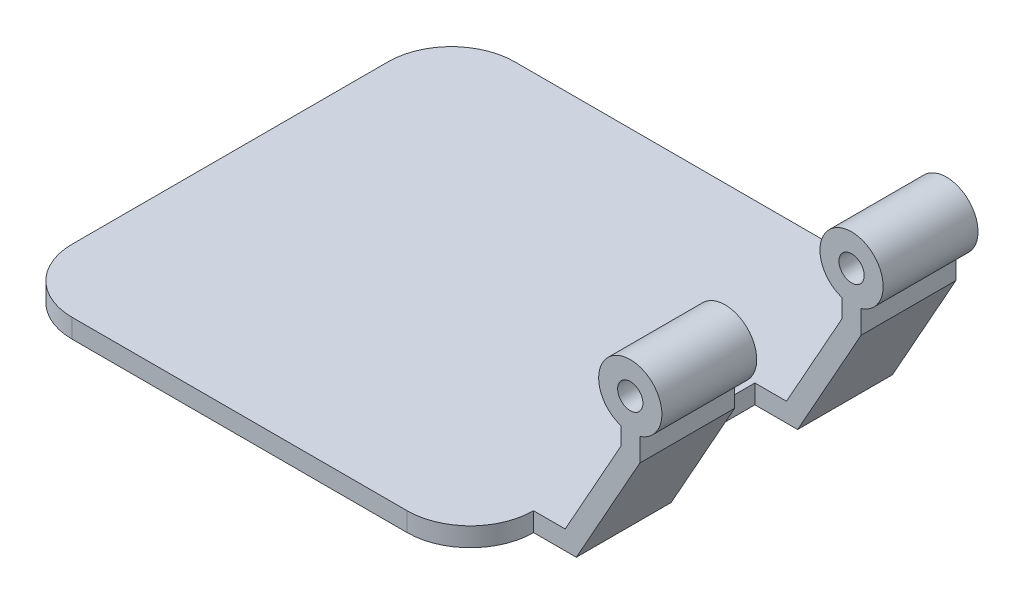
SolidWorks part; units mm, degrees
ref_plane "Front Plane" through (0, 0, 0) normal (0, 0, 1) x (1, 0, 0)
ref_plane "Top Plane" through (0, 0, 0) normal (0, 1, 0) x (1, 0, 0)
ref_plane "Right Plane" through (0, 0, 0) normal (1, 0, 0) x (0, 0, -1)
sketch "Sketch1" plane through (0, 0, 0) normal (0, 0, 1) x (1, 0, 0)
  line L0 (0, 3) -> (0, 0)
  line L1 (0, 0) -> (81.7588, 0)
  line L4 (88.7917, 18.7069) -> (80, 3)
  line L5 (80, 3) -> (0, 3)
  line L9 (81.7588, 0) -> (91.7917, 17.9244)
  line L11 (88.7917, 18.7069) -> (88.7917, 23.7069)
  line L12 (91.7917, 17.9244) -> (91.7917, 23.7069)
  line L13 (90.2917, 32.6026) -> (90.2917, 7.0815) construction
  line L14 (88.7917, 23.7069) -> (91.7917, 23.7069)
  circle A0 centre (90.2917, 26.3526) radius 5
  dimension "D9" = 10
  dimension "D1" = 80
  dimension "D2" = 3
  dimension "D3" = 18
  dimension "D4" = 3
  dimension "D5" = 119.237
  dimension "D6" = 5
  dimension "D7" = 3
  dimension "D8" = 1.5
extrude "Boss-Extrude1" add sketch "Sketch1" along normal blind 50 contours L9 L12 L14 L11 L4 L5 L0 L1 | A0
sketch "Sketch2" plane through (0, 0, 0) normal (0, 0, 1) x (1, 0, 0)
  circle A1 centre (90.2917, 26.3526) radius 2
  arc A2 (91.7917, 21.5829) -> (88.7917, 21.5829) centre (90.2917, 26.3526) ccw construction
  point P2 (88.697, 32.4609)
  point P11 (98.7108, 32.4609)
  point P12 (89.1184, 32.4609)
  point P13 (0, 0)
  point P14 (88.697, 32.4609)
  point P15 (88.697, 32.4609)
  dimension "D3" = 4
extrude "Cut-Extrude1" cut sketch "Sketch2" along normal through all
sketch "Sketch7" plane through (62.2541, -34.846, 0) normal (0.8726, -0.4884, 0) x (0, 0, -1)
  line L0 (-35, 89.9022) -> (-35, 28.0637) construction
  line L1 (-15, 89.9022) -> (-15, 25.2431) construction
  line L2 (-50, 39.9334) -> (-50, 60.4747) construction
  line L3 (0, 39.9334) -> (0, 60.4747) construction
  line L4 (-50, 39.9334) -> (0, 39.9334) construction
  line L5 (-35, 79.9206) -> (-15, 79.9206)
  line L6 (-35, 79.9206) -> (-35, 39.9334)
  line L7 (-35, 39.9334) -> (-15, 39.9334)
  line L8 (-15, 79.9206) -> (-15, 39.9334)
  point P6 (-35, 58.9829)
  dimension "D1" = 15
  dimension "D2" = 15
extrude "Cut-Extrude3" cut sketch "Sketch7" against normal blind 10 and the other way blind 10
sketch "Sketch8" plane through (0, 0, 0) normal (0, 0, 1) x (1, 0, 0)
  line L0 (66.951, 3) -> (66.951, 0)
  line L1 (80, 3) -> (0, 3) construction
  line L2 (0, 0) -> (81.7588, 0) construction
  line L3 (66.951, 0) -> (81.7588, 0)
  line L4 (81.7588, 0) -> (79.254, 1.6672)
  line L5 (88.7917, 18.7069) -> (80, 3) construction
  line L6 (79.254, 1.6672) -> (80, 3)
  line L7 (80, 3) -> (66.951, 3)
extrude "Boss-Extrude2" add sketch "Sketch8" along normal through all
sketch "Sketch9" plane through (0, 0, 0) normal (1, 0, 0) x (0, 0, -1)
  line L0 (-35, 21.5829) -> (-35, 31.3526) construction
  line L1 (-35, 37.4609) -> (-15, 37.4609)
  line L2 (-35, 37.4609) -> (-35, 26.5645)
  line L3 (-35, 26.5645) -> (-15, 26.5645)
  line L4 (-15, 37.4609) -> (-15, 26.5645)
  line L5 (-15, 17.9244) -> (-15, 21.5829) construction
extrude "Cut-Extrude4" cut sketch "Sketch9" along normal up to next
sketch "Sketch11" plane through (0, 0, 50) normal (0, 0, 1) x (1, 0, 0)
  line L0 (80, 3) -> (0, 3) construction
  line L1 (0, 0) -> (5, 0)
  line L2 (0, 0) -> (0, 3)
  line L3 (0, 3) -> (5, 3)
  line L4 (5, 0) -> (5, 3)
  point P7 (5, 1.5)
  dimension "D1" = 5
extrude "Cut-Extrude6" cut sketch "Sketch11" against normal up to body separate body
sketch "Sketch12" plane through (0, 3, 0) normal (0, 1, 0) x (1, 0, 0)
  line L0 (80, -15) -> (80, 0) construction
  line L1 (2, 10) -> (75, 10)
  line L2 (2, 10) -> (2, -60)
  line L3 (2, -60) -> (75, -60)
  line L4 (75, 10) -> (75, -60)
  line L6 (80, 0) -> (5, 0) construction
  line L7 (80, -50) -> (5, -50) construction
  line L8 (5, 0) -> (5, -50) construction
  dimension "D1" = 5
  dimension "D2" = 10
  dimension "D3" = 10
  dimension "D4" = 3
extrude "Boss-Extrude3" add sketch "Sketch12" against normal through all
sketch "Sketch13" plane through (0, 3, 0) normal (0, 1, 0) x (1, 0, 0)
  line L0 (75, 0) -> (75, -50) construction
  line L1 (81.7588, -15) -> (75, -15) construction
  line L2 (81.7588, -35) -> (75, -35) construction
  line L4 (75, -15) -> (81.7588, -15)
  line L5 (75, -15) -> (75, -35)
  line L6 (75, -35) -> (81.7588, -35)
  line L7 (81.7588, -15) -> (81.7588, -35)
extrude "Cut-Extrude7" cut sketch "Sketch13" against normal through all
fillet "Fillet1" radius 10 4 edges at (75, 1.5, -10) (2, 1.5, -10) (2, 1.5, 60) (75, 1.5, 60)
